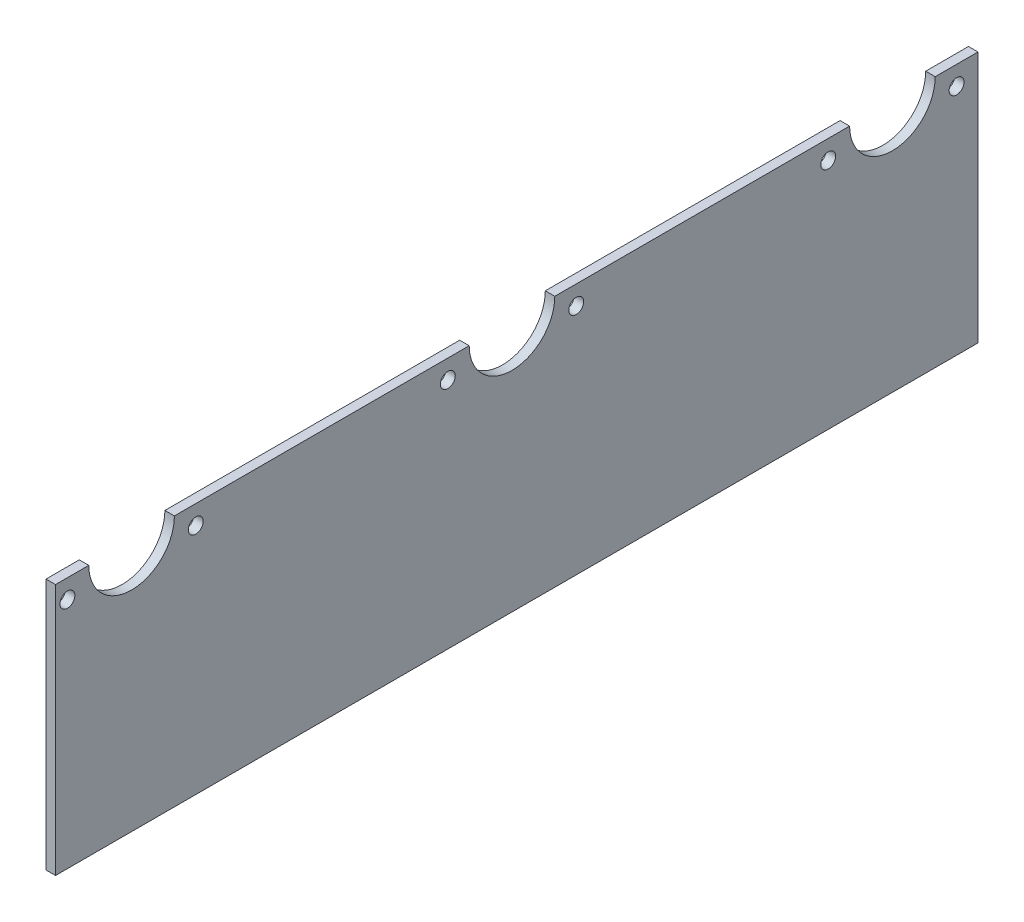
SolidWorks part; units mm, degrees
material "6061 Alloy"
ref_plane "Front Plane" through (0, 0, 0) normal (0, 0, 1) x (1, 0, 0)
ref_plane "Top Plane" through (0, 0, 0) normal (0, 1, 0) x (1, 0, 0)
ref_plane "Right Plane" through (0, 0, 0) normal (1, 0, 0) x (0, 0, -1)
sketch "Sketch1" plane through (0, 0, 0) normal (1, 0, 0) x (0, 0, -1)
  line L0 (153.9875, 0) -> (-153.9875, 0)
  line L1 (-153.9875, 0) -> (-153.9875, 84.1375)
  line L2 (-153.9875, 84.1375) -> (-142.875, 84.1375)
  line L3 (-114.3, 84.1375) -> (-15.875, 84.1375)
  line L4 (12.7, 84.1375) -> (111.125, 84.1375)
  line L5 (139.7, 84.1375) -> (153.9875, 84.1375)
  line L6 (153.9875, 84.1375) -> (153.9875, 0)
  line L7 (-153.9875, 25.4) -> (153.9875, 25.4) construction
  arc A6 (-142.875, 84.1375) -> (-114.3, 84.1375) centre (-128.5875, 84.1375) ccw
  arc A7 (-15.875, 84.1375) -> (12.7, 84.1375) centre (-1.5875, 84.1375) ccw
  arc A8 (111.125, 84.1375) -> (139.7, 84.1375) centre (125.4125, 84.1375) ccw
  point P4 (0, 0)
  dimension "D1" = 25.4
  dimension "D3" = 14.2875
  dimension "D5" = 28.575
  dimension "D6" = 44.45
  dimension "D2" = 307.975
  dimension "D4" = 127
extrude "Boss-Extrude1" add sketch "Sketch1" along normal blind 3.175
hole_wizard "#10 Clearance Hole1" positions "Sketch2" profile "Sketch3" hole size "#10" standard "ANSI Inch" end condition through all
sketch "Sketch2" plane through (3.175, 0, 0) normal (1, 0, 0) x (0, 0, -1)
  line L0 (-150.0187, 77.7875) -> (-107.1562, 77.7875) construction
  line L2 (-23.0187, 77.7875) -> (19.8438, 77.7875) construction
  line L4 (103.9813, 77.7875) -> (146.8438, 77.7875) construction
  line L6 (-142.875, 84.1375) -> (-153.9875, 84.1375) construction
  line L7 (-128.5875, 77.7875) -> (-128.5875, 84.1375) construction
  line L9 (-1.5875, 84.1375) -> (-1.5875, 77.7875) construction
  line L11 (125.4125, 84.1375) -> (125.4125, 77.7875) construction
  point P0 (-150.0187, 77.7875)
  point P2 (-107.1562, 77.7875)
  point P4 (-23.0187, 77.7875)
  point P6 (19.8438, 77.7875)
  point P8 (103.9813, 77.7875)
  point P10 (146.8438, 77.7875)
  dimension "D1" = 42.8625
  dimension "D2" = 6.35
sketch "Sketch3" plane through (3.175, 77.7875, 150.0187) normal (0, 1, 0) x (0, 0, -1)
  line L0 (0, 0) -> (0, 3.175)
  line L1 (0, 3.175) -> (2.4892, 3.175)
  line L2 (2.4892, 3.175) -> (2.4892, 0)
  line L5 (2.4892, 0) -> (0, 0)
  line L11 (0, -6.35) -> (0, 107.95) construction
  dimension "Thru Hole Dia." = 4.9784
  dimension "Thru Hole Depth" = 3.175
